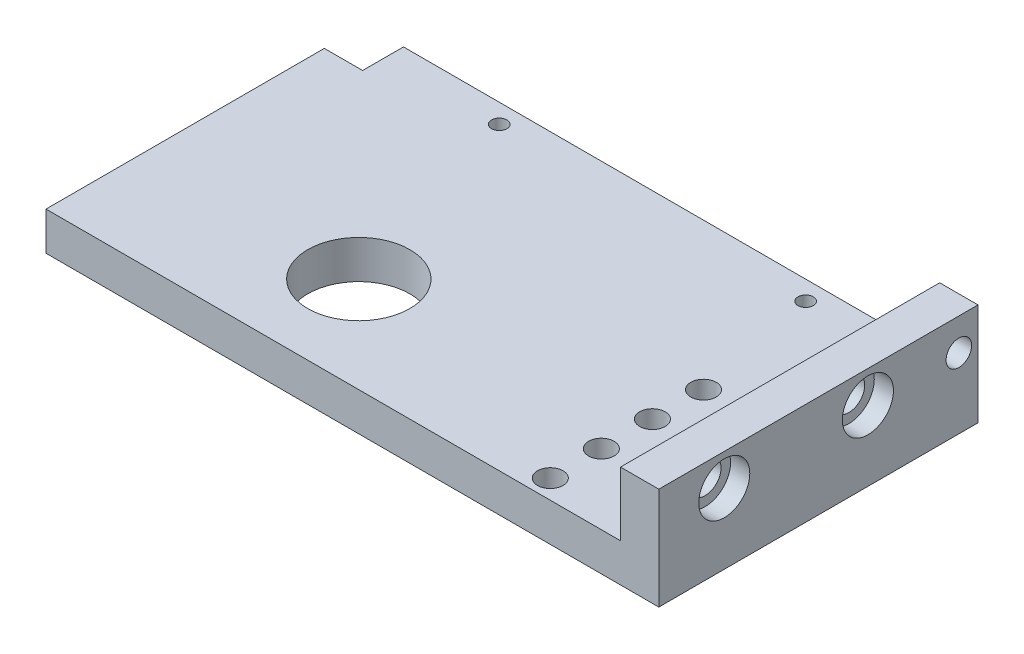
SolidWorks part; units mm, degrees
ref_plane "前视基准面" through (0, 0, 0) normal (0, 0, 1) x (1, 0, 0)
ref_plane "上视基准面" through (0, 0, 0) normal (0, 1, 0) x (1, 0, 0)
ref_plane "右视基准面" through (0, 0, 0) normal (1, 0, 0) x (0, 0, -1)
other "Configuration Table"
sketch "草图1" plane through (0, 0, 0) normal (0, 1, 0) x (1, 0, 0)
  line L1 (-22.5, -11) -> (22.5, -11)
  line L2 (-22.5, -11) -> (-22.5, 11)
  line L3 (-22.5, 11) -> (22.5, 11)
  line L4 (22.5, -11) -> (22.5, 11)
  line L5 (-22.5, -11) -> (22.5, 11) construction
  line L6 (-22.5, 11) -> (22.5, -11) construction
  line L11 (22.5, 11) -> (-19.5, 11)
  line L12 (22.5, 11) -> (22.5, 14)
  line L13 (22.5, 14) -> (-19.5, 14)
  line L14 (-19.5, 11) -> (-19.5, 14)
  point P0 (0, 0)
  dimension "D3" = 42
  dimension "D1" = 45
  dimension "D2" = 3
  dimension "D5" = 22
extrude "凸台-拉伸1" add sketch "草图1" along normal blind 3 contours L3 L4 L1 L2 | L12 L13 L14 L11
sketch "草图2" plane through (22.5, 0, 0) normal (1, 0, 0) x (0, 0, -1)
  line L0 (-11, 3) -> (-11, 0) construction
  line L1 (-11, 0) -> (14, 0)
  line L2 (-11, 0) -> (-11, 8)
  line L3 (-11, 8) -> (14, 8)
  line L4 (14, 0) -> (14, 8)
  line L5 (-11, 0) -> (14, 0) construction
  line L6 (14, 3) -> (14, 0) construction
  point P8 (0, 0)
  dimension "D1" = 8
extrude "凸台-拉伸2" add sketch "草图2" along normal blind 3
sketch "草图3" plane through (25.5, 0, 0) normal (1, 0, 0) x (0, 0, -1)
  circle A4 centre (5.375, 5.5) radius 1.25
  circle A5 centre (5.375, 5.5) radius 2
  circle A6 centre (-5.875, 5.5) radius 1.25
  circle A7 centre (-5.875, 5.5) radius 2
  point P6 (0, 0)
  point P7 (0, 0)
  point P8 (0, 0)
  point P9 (-6.1201, 4.0786)
  point P10 (5.375, 5.5)
  point P11 (-5.875, 5.5)
  dimension "D1" = 2.5
  dimension "D2" = 4
extrude "切除-拉伸1" cut sketch "草图3" against normal through all contours A4 | A6
extrude "切除-拉伸2" cut sketch "草图3<3>" against normal blind 1.5 contours A5 | A7
sketch "草图3<3>" plane through (25.5, 0, 0) normal (1, 0, 0) x (0, 0, -1) same geometry as "草图3"
sketch "草图4" plane through (25.5, 0, 0) normal (1, 0, 0) x (0, 0, -1)
  circle A0 centre (12.5, 5.5) radius 0.6
  circle A1 centre (12.5, 5.5) radius 1
  point P0 (12.5, 5.5)
  point P3 (0, 0)
  point P6 (12.5, 5.95)
  dimension "D1" = 1.2
  dimension "D2" = 2
extrude "切除-拉伸3" cut sketch "草图4" against normal through all contours A0
extrude "切除-拉伸4" cut sketch "草图4<3>" against normal blind 1.5 contours A1
sketch "草图4<3>" plane through (25.5, 0, 0) normal (1, 0, 0) x (0, 0, -1) same geometry as "草图4"
sketch "草图5" plane through (0, 0, 0) normal (0, -1, 0) x (1, 0, 0)
  line L0 (-22.5, 11) -> (-22.5, -11) construction
  line L1 (-22.5, -11) -> (-19.5, -11)
  line L2 (-22.5, -11) -> (-22.5, -10.8)
  line L3 (-22.5, -10.8) -> (-19.5, -10.8)
  line L4 (-19.5, -11) -> (-19.5, -10.8)
  line L5 (-22.5, -11) -> (-19.5, -11) construction
  line L6 (-19.5, -11) -> (-19.5, -14) construction
  point P8 (-19.7678, -11)
  dimension "D1" = 0.2
extrude "切除-拉伸5" cut sketch "草图5" against normal through all
sketch "草图6" plane through (0, 0, 0) normal (0, -1, 0) x (1, 0, 0)
  line L0 (25.5, -14) -> (-19.5, -14) construction
  line L1 (25.5, -12.5) -> (13.5, -12.5) construction
  line L2 (25.5, 11) -> (25.5, -14) construction
  line L3 (13.5, -12.5) -> (1.5, -12.5) construction
  line L4 (1.5, -12.5) -> (-10.5, -12.5) construction
  line L5 (-10.5, -12.5) -> (-22.5, -12.5) construction
  line L6 (-22.5, 11) -> (-22.5, -10.8) construction
  circle A0 centre (-10.5, -12.5) radius 0.6
  circle A1 centre (-10.5, -12.5) radius 1
  circle A2 centre (13.5, -12.5) radius 0.6
  circle A3 centre (13.5, -12.5) radius 1
  dimension "D1" = 1.2
  dimension "D2" = 2
  dimension "D3" = 1.5
extrude "切除-拉伸6" cut sketch "草图6" against normal through all contours A0 | A2
extrude "切除-拉伸7" cut sketch "草图6<3>" against normal blind 1.5 contours A1 | A3
sketch "草图6<3>" plane through (0, 0, 0) normal (0, -1, 0) x (1, 0, 0) same geometry as "草图6"
sketch "草图7" plane through (0, 0, 0) normal (0, -1, 0) x (1, 0, 0)
  line L0 (25.5, 11) -> (25.5, -14) construction
  line L1 (21, 11) -> (21, 4.75) construction
  line L2 (-22.5, 11) -> (25.5, 11) construction
  line L3 (21, 4.75) -> (21, -1.5) construction
  line L4 (21, -1.5) -> (21, -7.75) construction
  line L5 (21, -7.75) -> (21, -14) construction
  line L6 (25.5, -14) -> (-19.5, -14) construction
  circle A0 centre (21, 4.75) radius 0.35
  circle A1 centre (21, -7.75) radius 0.35
  dimension "D1" = 0.7
  dimension "D2" = 4.5
extrude "切除-拉伸8" cut sketch "草图7" against normal blind 3
sketch "草图8" plane through (0, 0, 0) normal (0, -1, 0) x (1, 0, 0)
  line L0 (-22.5, 11) -> (25.5, 11) construction
  line L1 (15.5, 9.5) -> (15.5, 5.5) construction
  line L2 (15.5, 5.5) -> (15.5, 1.5) construction
  line L3 (25.5, 11) -> (25.5, -14) construction
  line L4 (15.5, 1.5) -> (15.5, -2.5) construction
  line L5 (-22.5, 11) -> (-22.5, -10.8) construction
  circle A0 centre (-5.5, 3.5) radius 4
  circle A1 centre (15.5, 9.5) radius 1
  circle A2 centre (15.5, 5.5) radius 1
  circle A3 centre (15.5, 1.5) radius 1
  circle A4 centre (15.5, -2.5) radius 1
  point P12 (15.5, 3.5)
  dimension "D2" = 8
  dimension "D3" = 2
  dimension "D1" = 7.5
  dimension "D4" = 4
  dimension "D5" = 10
  dimension "D6" = 17
extrude "切除-拉伸9" cut sketch "草图8" against normal through all
